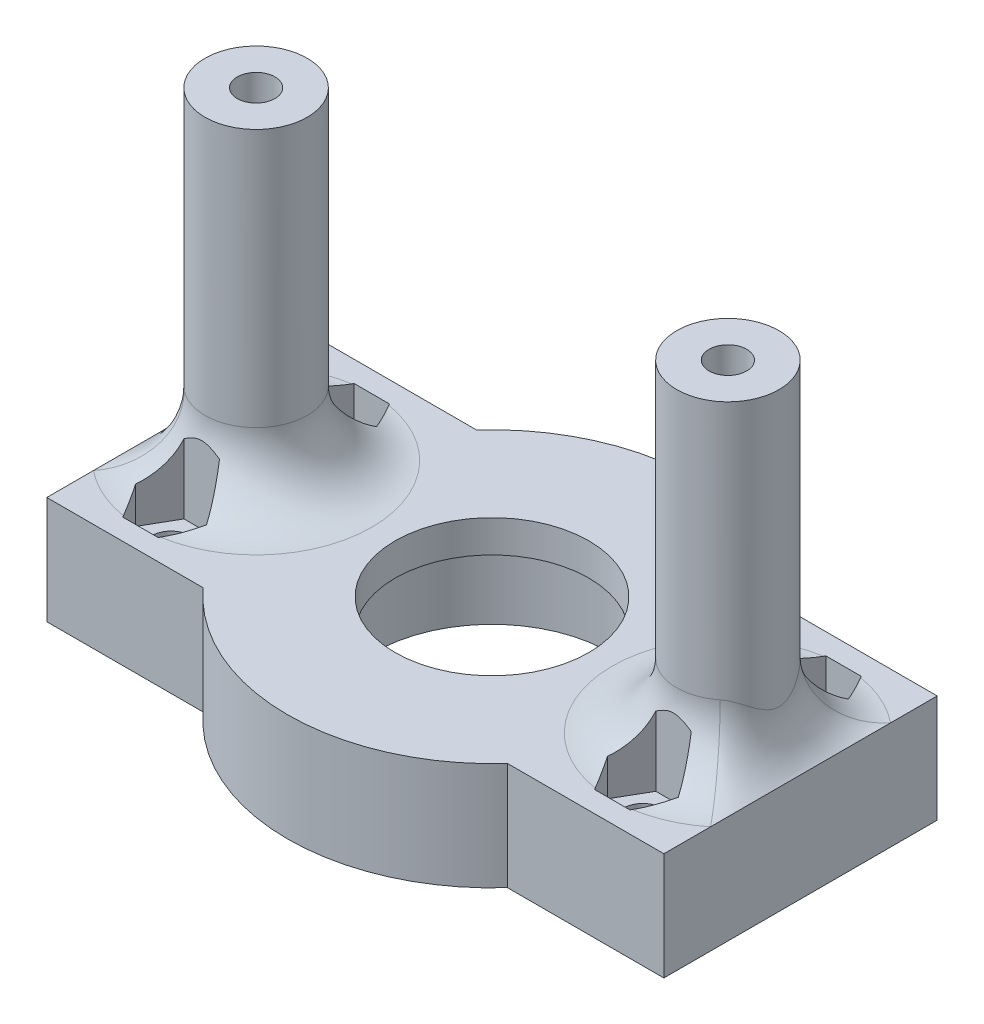
SolidWorks part; units mm, degrees
ref_plane "Front Plane" through (0, 0, 0) normal (0, 0, 1) x (1, 0, 0)
ref_plane "Top Plane" through (0, 0, 0) normal (0, 1, 0) x (1, 0, 0)
ref_plane "Right Plane" through (0, 0, 0) normal (1, 0, 0) x (0, 0, -1)
sketch "Sketch1" plane through (0, 0, 0) normal (0, 1, 0) x (1, 0, 0)
  line L0 (-21.9203, 0) -> (0, 0) construction
  line L1 (28.6703, -12.7) -> (14.1319, -12.7)
  line L2 (28.6703, -12.7) -> (28.6703, 12.7)
  line L3 (28.6703, 12.7) -> (14.1319, 12.7)
  line L4 (-28.6703, -12.7) -> (-28.6703, 12.7)
  line L5 (28.6703, -12.7) -> (-28.6703, 12.7) construction
  line L6 (28.6703, 12.7) -> (-28.6703, -12.7) construction
  line L7 (0, 0) -> (21.9203, 0) construction
  line L8 (-14.1319, -12.7) -> (-28.6703, -12.7)
  line L9 (-14.1319, 12.7) -> (-28.6703, 12.7)
  circle A0 centre (0, 0) radius 11
  arc A1 (-14.1319, -12.7) -> (14.1319, -12.7) centre (0, 0) ccw
  circle A2 centre (21.9203, 0) radius 1.75
  circle A3 centre (-21.9203, 0) radius 1.75
  arc A4 (14.1319, 12.7) -> (-14.1319, 12.7) centre (0, 0) ccw
  dimension "D1" = 22
  dimension "D3" = 3.5
  dimension "D2" = 25.4
  dimension "D4" = 8
  dimension "D5" = 43.8406
  dimension "D6" = 5
extrude "Boss-Extrude1" add sketch "Sketch1" along normal blind 10
sketch "Sketch2" plane through (0, 10, 0) normal (0, 1, 0) x (1, 0, 0)
  circle A0 centre (0, 0) radius 9
  circle A1 centre (0, 0) radius 11 construction
  circle A2 centre (0, 0) radius 11
  dimension "D1" = 2
extrude "Boss-Extrude2" add sketch "Sketch2" against normal blind 3
sketch "Sketch3" plane through (0, 10, 0) normal (0, 1, 0) x (1, 0, 0)
  circle A0 centre (-21.9203, 0) radius 4.75
  circle A1 centre (21.9203, 0) radius 4.75
  circle A2 centre (-21.9203, 0) radius 1.75 construction
  circle A3 centre (21.9203, 0) radius 1.75 construction
  circle A4 centre (-21.9203, 0) radius 1.75
  circle A5 centre (21.9203, 0) radius 1.75
  dimension "D1" = 3
extrude "Boss-Extrude3" add sketch "Sketch3" along normal blind 30
fillet "Fillet1" radius 6 2 edges at (21.9203, 10, 4.75) (-21.9203, 10, 4.75)
sketch "Sketch4" plane through (0, 0, 0) normal (0, -1, 0) x (1, 0, 0)
  circle A0 centre (-21.9203, 0) radius 2.85
  circle A1 centre (21.9203, 0) radius 2.85
  dimension "D1" = 5.7
extrude "Cut-Extrude1" cut sketch "Sketch4" against normal blind 3
sketch "Sketch5" plane through (0, 0, 0) normal (0, -1, 0) x (1, 0, 0)
  line L0 (-28.6703, 12.7) -> (-14.1319, 12.7) construction
  line L1 (-21.9203, -7.9) -> (21.9203, -7.9) construction
  line L2 (-21.9203, -7.9) -> (-21.9203, 7.9) construction
  line L3 (-21.9203, 7.9) -> (21.9203, 7.9) construction
  line L4 (21.9203, -7.9) -> (21.9203, 7.9) construction
  circle A0 centre (-21.9203, 7.9) radius 1.8
  circle A1 centre (21.9203, 7.9) radius 1.8
  circle A2 centre (21.9203, -7.9) radius 1.8
  circle A3 centre (-21.9203, -7.9) radius 1.8
  point P4 (-21.9203, 0)
  point P5 (21.9203, 0)
  point P7 (21.9203, 0)
  point P9 (-21.9203, 0)
  dimension "D2" = 3.6
  dimension "D1" = 3
extrude "Cut-Extrude2" cut sketch "Sketch5" against normal through all
sketch "Sketch6" plane through (0, 10, 0) normal (0, 1, 0) x (1, 0, 0)
  line L1 (-20.2749, 10.75) -> (-23.5658, 10.75)
  line L2 (-23.5658, 10.75) -> (-25.2112, 7.9)
  line L3 (-25.2112, 7.9) -> (-23.5658, 5.05)
  line L4 (-23.5658, 5.05) -> (-20.2749, 5.05)
  line L5 (-20.2749, 5.05) -> (-18.6294, 7.9)
  line L6 (-18.6294, 7.9) -> (-20.2749, 10.75)
  line L7 (23.5658, 10.75) -> (20.2749, 10.75)
  line L8 (20.2749, 10.75) -> (18.6294, 7.9)
  line L9 (18.6294, 7.9) -> (20.2749, 5.05)
  line L10 (20.2749, 5.05) -> (23.5658, 5.05)
  line L11 (23.5658, 5.05) -> (25.2112, 7.9)
  line L12 (25.2112, 7.9) -> (23.5658, 10.75)
  line L13 (25.2112, -7.9) -> (23.5658, -5.05)
  line L14 (23.5658, -5.05) -> (20.2749, -5.05)
  line L15 (20.2749, -5.05) -> (18.6294, -7.9)
  line L16 (18.6294, -7.9) -> (20.2749, -10.75)
  line L17 (20.2749, -10.75) -> (23.5658, -10.75)
  line L18 (23.5658, -10.75) -> (25.2112, -7.9)
  line L19 (-18.6294, -7.9) -> (-20.2749, -5.05)
  line L20 (-20.2749, -5.05) -> (-23.5658, -5.05)
  line L21 (-23.5658, -5.05) -> (-25.2112, -7.9)
  line L22 (-25.2112, -7.9) -> (-23.5658, -10.75)
  line L23 (-23.5658, -10.75) -> (-20.2749, -10.75)
  line L24 (-20.2749, -10.75) -> (-18.6294, -7.9)
  circle A0 centre (-21.9203, 7.9) radius 2.85 construction
  circle A1 centre (21.9203, 7.9) radius 2.85 construction
  circle A2 centre (21.9203, -7.9) radius 2.85 construction
  circle A3 centre (-21.9203, -7.9) radius 2.85 construction
  dimension "D1" = 5.7
extrude "Cut-Extrude3" cut sketch "Sketch6" against normal blind 3 and the other way through all
equation "\"D5@Sketch1\"=sqr(2)*31"
